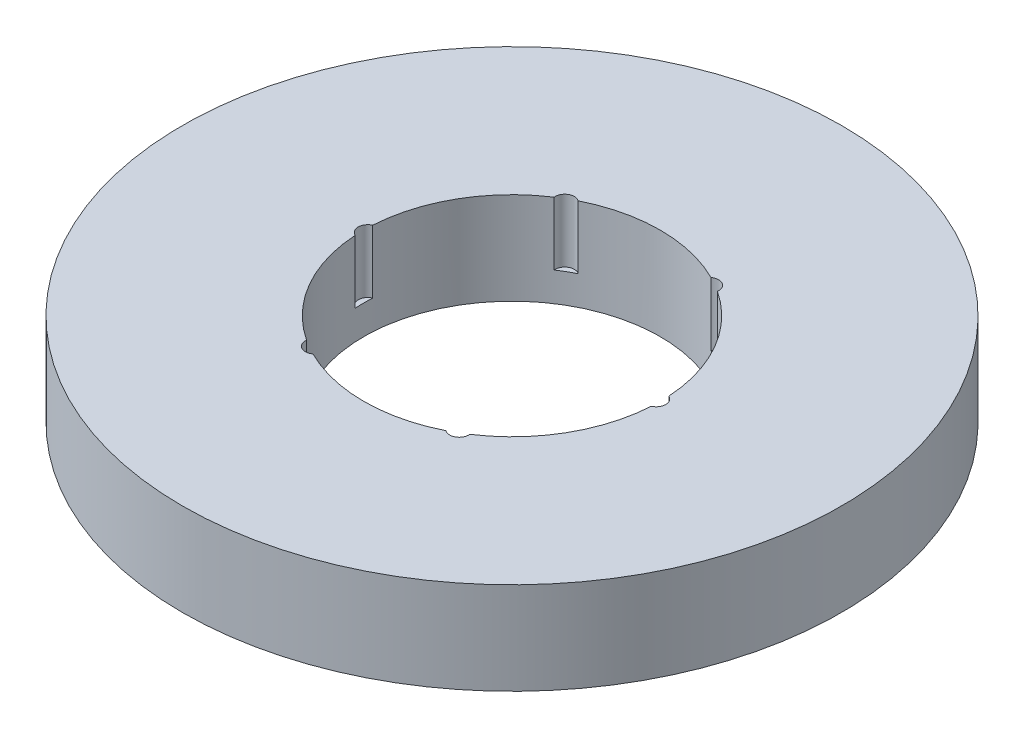
SolidWorks part; units mm, degrees
ref_plane "Front Plane" through (0, 0, 0) normal (0, 0, 1) x (1, 0, 0)
ref_plane "Top Plane" through (0, 0, 0) normal (0, 1, 0) x (1, 0, 0)
ref_plane "Right Plane" through (0, 0, 0) normal (1, 0, 0) x (0, 0, -1)
sketch "Sketch1" plane through (0, 0, 0) normal (0, 1, 0) x (1, 0, 0)
  circle A0 centre (0, 0) radius 100
  dimension "FLANGE_OD" = 200
extrude "Boss-Extrude1" add sketch "Sketch1" along normal blind 28
sketch "Sketch2" plane through (0, 0, 0) normal (0, 1, 0) x (1, 0, 0)
  circle A0 centre (0, 0) radius 45
  dimension "BORE_D" = 90
extrude "Cut-Extrude1" cut sketch "Sketch2" along normal through all
sketch "Sketch3" plane through (0, 28, 0) normal (0, 1, 0) x (1, 0, 0)
  circle A0 centre (0, 0) radius 43.7525 construction
  circle A1 centre (-43.7525, 0) radius 2.9082
  dimension "BOLT_D" = 5.8165
  dimension "BOLT_PCD" = 87.505
extrude "Cut-Extrude2" cut sketch "Sketch3" against normal blind 19.1531
pattern_circular "CirPattern1" count 6 over 360 about axis through (0, 0, 0) along (0, 1, 0) of "Cut-Extrude2"
